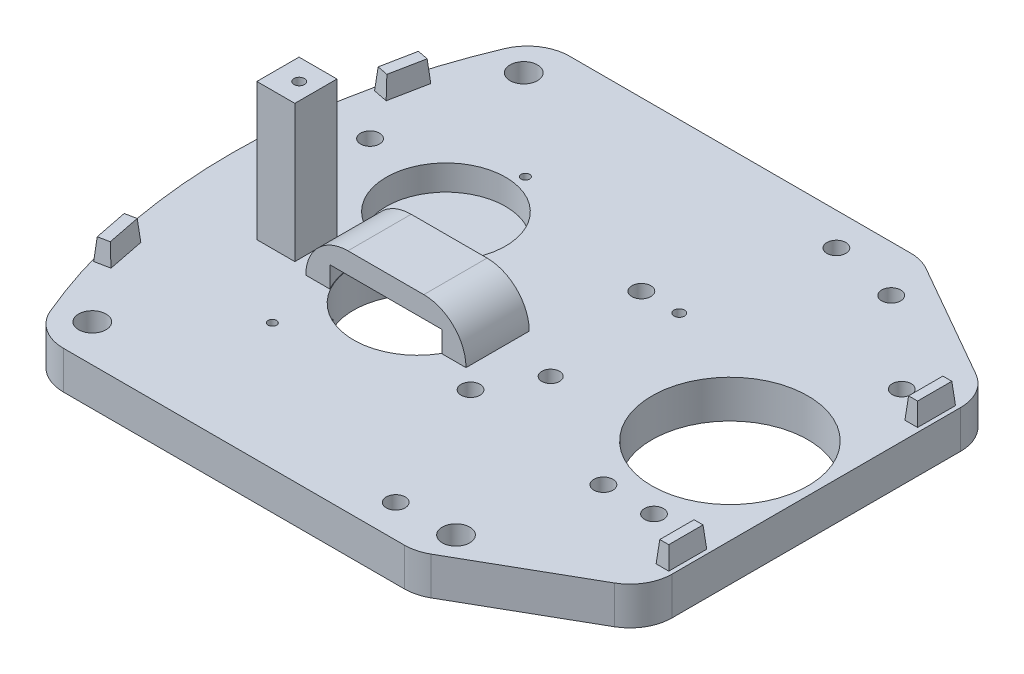
SolidWorks part; units mm, degrees
ref_plane "Front" through (0, 0, 0) normal (0, 0, 1) x (1, 0, 0)
ref_plane "Top" through (0, 0, 0) normal (0, 1, 0) x (1, 0, 0)
ref_plane "Right" through (0, 0, 0) normal (1, 0, 0) x (0, 0, -1)
sketch "Sketch1" plane through (0, 0, 0) normal (0, 1, 0) x (1, 0, 0)
  line L0 (125, 60) -> (3.8854, 60) construction
  line L1 (0, 0) -> (125, 0)
  line L2 (0, 0) -> (0, 120)
  line L3 (0, 120) -> (125, 120)
  line L4 (125, 0) -> (125, 120)
  line L5 (3.8854, 127.5) -> (3.8854, -7.5) construction
  arc A0 (3.8854, 127.5) -> (3.8854, -7.5) centre (125, 60) ccw
  dimension "D1" = 125
  dimension "D2" = 120
  dimension "D3" = 135
extrude "Top_Base" add sketch "Sketch1" along normal blind 9 contours L2 A0 | L1 L4 L3 L2 region at (62.5, 0, -60) region at (-5.4854, 0, -60)
sketch "Fingers_Position" plane through (0, 9, 0) normal (0, 1, 0) x (1, 0, 0)
  line L5 (67.75, 3.25) -> (12.75, 3.25) construction
  line L6 (67.75, 3.25) -> (67.75, 35.25) construction
  line L7 (67.75, 35.25) -> (12.75, 35.25) construction
  line L8 (12.75, 3.25) -> (12.75, 35.25) construction
  line L10 (67.75, 19.25) -> (26, 19.25) construction
  line L11 (77.75, 104.5) -> (77.75, 49.5) construction
  line L12 (35.75, 35.25) -> (35.75, 3.25) construction
  line L13 (40.75, 35.25) -> (40.75, 3.25) construction
  line L14 (125, 60) -> (-13.6542, 60) construction
  line L15 (35.75, 84.75) -> (35.75, 116.75) construction
  line L16 (26, 19.25) -> (26, 30) construction
  line L18 (77.75, 49.5) -> (109.75, 49.5) construction
  line L19 (109.75, 49.5) -> (109.75, 104.5) construction
  line L20 (109.75, 104.5) -> (77.75, 104.5) construction
  line L21 (92.5, 69) -> (92.5, 31) construction
  line L22 (92.5, 31) -> (116.5, 31) construction
  line L23 (116.5, 31) -> (116.5, 69) construction
  line L24 (116.5, 69) -> (92.5, 69) construction
  line L25 (93.75, 104.5) -> (93.75, 60) construction
  line L26 (104.5, 31) -> (104.5, 60) construction
  line L27 (26, 100.75) -> (26, 90) construction
  line L28 (40.75, 84.75) -> (40.75, 116.75) construction
  line L29 (67.75, 100.75) -> (26, 100.75) construction
  line L30 (12.75, 116.75) -> (12.75, 84.75) construction
  line L31 (67.75, 84.75) -> (12.75, 84.75) construction
  line L32 (67.75, 116.75) -> (67.75, 84.75) construction
  line L33 (67.75, 116.75) -> (12.75, 116.75) construction
  line L34 (26, 72.5) -> (26, 47.5) construction
  line L35 (92.5, 36) -> (98.5, 36) construction
  line L36 (98.5, 36) -> (98.5, 31) construction
  line L37 (116.5, 36) -> (110.5, 36) construction
  line L38 (110.5, 36) -> (110.5, 31) construction
  line L39 (93.75, 60) -> (104.5, 60) construction
  line L40 (77.75, 77.5) -> (109.75, 77.5) construction
  line L41 (125, 0) -> (125, 120) construction
  line L42 (67.75, 75.75) -> (58.75, 75.75) construction
  line L43 (67.75, 35.25) -> (58.75, 35.25) construction
  line L44 (67.75, 35.25) -> (67.75, 44.25) construction
  line L45 (67.75, 44.25) -> (58.75, 44.25) construction
  line L46 (58.75, 35.25) -> (58.75, 44.25) construction
  line L47 (58.75, 84.75) -> (58.75, 75.75) construction
  line L48 (67.75, 84.75) -> (58.75, 84.75) construction
  line L49 (67.75, 84.75) -> (67.75, 75.75) construction
  circle A1 centre (26, 30) radius 16.25 construction
  circle A3 centre (26, 30) radius 17.5 construction
  circle A5 centre (26, 30) radius 15 construction
  circle A6 centre (104.5, 60) radius 9 construction
  circle A7 centre (104.5, 60) radius 17.75 construction
  circle A8 centre (26, 30) radius 1 construction
  circle A9 centre (39.1696, 51.25) radius 7.5 construction
  circle A10 centre (39.1696, 51.25) radius 8.75 construction
  circle A11 centre (39.1696, 51.25) radius 10 construction
  circle A12 centre (39.1696, 68.75) radius 10 construction
  circle A13 centre (39.1696, 68.75) radius 8.75 construction
  circle A14 centre (39.1696, 68.75) radius 7.5 construction
  circle A15 centre (26, 90) radius 1 construction
  circle A16 centre (26, 90) radius 15 construction
  circle A17 centre (26, 90) radius 17.5 construction
  circle A18 centre (26, 90) radius 16.25 construction
  circle A19 centre (98.5, 36) radius 2.25 construction
  circle A20 centre (110.5, 36) radius 2.25 construction
  arc A21 (0, 120) -> (0, 0) centre (125, 60) ccw construction
  dimension "D3" = 32.5
  dimension "D4" = 35
  dimension "D6" = 30
  dimension "D10" = 18
  dimension "D11" = 35.5
  dimension "D19" = 2
  dimension "D20" = 20
  dimension "D21" = 17.5
  dimension "D22" = 15
  dimension "D29" = 4.5
  dimension "D5" = 32
  dimension "D7" = 55
  dimension "D8" = 24
  dimension "D9" = 38
  dimension "D14" = 10
  dimension "D2" = 27
  dimension "D15" = 55
  dimension "D16" = 32
  dimension "D17" = 41.75
  dimension "D18" = 10.75
  dimension "D23" = 25
  dimension "D13" = 29
  dimension "D25" = 6
  dimension "D26" = 6
  dimension "D27" = 5
  dimension "D28" = 5
  dimension "D12" = 44.5
  dimension "D30" = 10.75
  dimension "D31" = 27
  dimension "D24" = 8.5
  dimension "D32" = 32
  dimension "D33" = 9
  dimension "D34" = 9
sketch "Intermediate_Gear_Position" plane through (0, 9, 0) normal (0, 1, 0) x (1, 0, 0)
  line L0 (-5.25, 73.4139) -> (23.75, 73.4139) construction
  line L1 (35.75, 84.75) -> (35.75, 116.75) construction
  line L2 (32.75, 85.4139) -> (32.75, 61.4139) construction
  line L3 (-0.25, 79.4139) -> (-0.25, 85.4139) construction
  line L4 (32.75, 85.4139) -> (-5.25, 85.4139) construction
  line L6 (-5.25, 85.4139) -> (-5.25, 61.4139) construction
  line L7 (32.75, 61.4139) -> (-5.25, 61.4139) construction
  line L21 (-0.25, 67.4139) -> (-0.25, 61.4139) construction
  circle A0 centre (39.1696, 51.25) radius 14 construction
  circle A4 centre (39.1696, 51.25) radius 15 construction
  circle A6 centre (23.75, 73.4139) radius 14 construction
  circle A8 centre (39.1696, 51.25) radius 13 construction
  circle A10 centre (-0.25, 67.4139) radius 2.25 construction
  circle A11 centre (23.75, 73.4139) radius 13 construction
  circle A12 centre (-0.25, 79.4139) radius 2.25 construction
  circle A13 centre (23.75, 73.4139) radius 12 construction
  dimension "D2" = 30
  dimension "D6" = 28
  dimension "D4" = 26
  dimension "D18" = 4.5
  dimension "D22" = 4.5
  dimension "D3" = 28
  dimension "D10" = 26
  dimension "D11" = 24
  dimension "D8" = 38
  dimension "D5" = 6
  dimension "D7" = 24
  dimension "D16" = 5
  dimension "D19" = 6
  dimension "D21" = 5
  dimension "D9" = 29
  dimension "D12" = 3
sketch "Sketch5" plane through (0, 9, 0) normal (0, 1, 0) x (1, 0, 0)
  circle A1 centre (23.75, 73.4139) radius 14.15
  dimension "D1" = 28.3
extrude "Drive_Gear_Hole" cut sketch "Sketch5" against normal blind 6
sketch "Sketch8" plane through (0, 9, 0) normal (0, 1, 0) x (1, 0, 0)
  circle A1 centre (104.5, 60) radius 18.5
  dimension "D2" = 37
sketch "Sketch28" plane through (0, 9, 0) normal (0, 1, 0) x (1, 0, 0)
  circle A0 centre (39.1696, 51.25) radius 15.15
  dimension "D1" = 30.3
extrude "Two_Stage_Gear_Hole" cut sketch "Sketch28" against normal through all
extrude "XL320_Finger_Knuckle_Mount" cut sketch "Sketch8" against normal through all
sketch "XL320_Mount_Holes" plane through (0, 9, 0) normal (0, 1, 0) x (1, 0, 0)
  line L0 (116.5, 36) -> (110.5, 36) construction
  circle A13 centre (110.5, 36) radius 2.25
  circle A15 centre (98.5, 36) radius 2.25
  circle A16 centre (-0.25, 79.4139) radius 2.25
  circle A17 centre (-0.25, 67.4139) radius 2.25
  dimension "D5" = 4.5
sketch "AX12_Mount_Holes" plane through (0, 9, 0) normal (0, 1, 0) x (1, 0, 0)
  line L0 (67.75, 116.75) -> (77.5, 116.75) construction
  line L1 (67.75, 116.75) -> (12.75, 116.75) construction
  line L2 (77.5, 116.75) -> (77.5, 112.25) construction
  line L3 (67.75, 84.75) -> (67.75, 80.25) construction
  line L4 (67.75, 80.25) -> (63.25, 80.25) construction
  line L5 (93.75, 104.5) -> (93.75, 109) construction
  line L6 (109.75, 104.5) -> (114.25, 104.5) construction
  line L7 (109.75, 104.5) -> (77.75, 104.5) construction
  line L8 (114.25, 104.5) -> (114.25, 91) construction
  line L9 (77.5, 3.25) -> (67.75, 3.25) construction
  line L10 (67.75, 35.25) -> (67.75, 39.75) construction
  line L11 (67.75, 39.75) -> (63.25, 39.75) construction
  line L13 (67.75, 3.25) -> (12.75, 3.25) construction
  line L14 (77.5, 3.25) -> (77.5, 7.75) construction
  circle A4 centre (77.5, 112.25) radius 2.25
  circle A5 centre (63.25, 80.25) radius 2.25
  circle A6 centre (114.25, 91) radius 2.25
  circle A7 centre (93.75, 109) radius 2.25
  circle A8 centre (63.25, 39.75) radius 2.25
  circle A9 centre (77.5, 7.75) radius 2.25
  dimension "D3" = 4.5
  dimension "D4" = 13.5
  dimension "D2" = 4.5
  dimension "D6" = 4.5
  dimension "D1" = 9.75
  dimension "D5" = 9.75
sketch "Sketch26" plane through (0, 9, 0) normal (0, -1, 0) x (1, 0, 0)
  line L0 (26, -12.5) -> (26, -30) construction
  line L2 (-13.6542, -60) -> (125, -60) construction
  circle A0 centre (26, -30) radius 17.5 construction
  circle A1 centre (26, -30) radius 1
  circle A2 centre (26, -90) radius 1
  dimension "D2" = 2
extrude "String_Holes" cut sketch "Sketch26" along normal through all
extrude "XL320_Mount_Holes_(M4)" cut sketch "XL320_Mount_Holes" against normal through all
extrude "AX12_Mount_Holes_(M4)" cut sketch "AX12_Mount_Holes" against normal through all
sketch "Sketch27" plane through (0, 0, 0) normal (0, -1, 0) x (1, 0, 0)
  line L0 (110.5, -31.6699) -> (106.75, -33.8349)
  line L2 (106.75, -33.8349) -> (106.75, -38.1651)
  line L3 (106.75, -38.1651) -> (110.5, -40.3301)
  line L5 (110.5, -40.3301) -> (114.25, -38.1651)
  line L6 (114.25, -38.1651) -> (114.25, -33.8349)
  line L8 (114.25, -33.8349) -> (110.5, -31.6699)
  line L13 (110.5, -31.6699) -> (110.5, -40.3301) construction
  line L14 (106.75, -33.8349) -> (114.25, -38.1651) construction
  line L16 (114.25, -33.8349) -> (106.75, -38.1651) construction
  line L17 (98.5, -31.6699) -> (94.75, -33.8349)
  line L18 (94.75, -33.8349) -> (102.25, -38.1651) construction
  line L19 (94.75, -33.8349) -> (94.75, -38.1651)
  line L20 (102.25, -33.8349) -> (94.75, -38.1651) construction
  line L21 (98.5, -31.6699) -> (98.5, -40.3301) construction
  line L22 (102.25, -38.1651) -> (102.25, -33.8349)
  line L23 (94.75, -38.1651) -> (98.5, -40.3301)
  line L24 (98.5, -40.3301) -> (102.25, -38.1651)
  line L25 (102.25, -33.8349) -> (98.5, -31.6699)
  line L26 (3.5, -65.2488) -> (-0.25, -63.0837)
  line L27 (3.5, -69.5789) -> (3.5, -65.2488)
  line L28 (-4, -65.2488) -> (-4, -69.5789)
  line L29 (-0.25, -63.0837) -> (-0.25, -71.744) construction
  line L30 (-4, -65.2488) -> (3.5, -69.5789) construction
  line L31 (-0.25, -63.0837) -> (-4, -65.2488)
  line L32 (-0.25, -71.744) -> (3.5, -69.5789)
  line L33 (-4, -69.5789) -> (-0.25, -71.744)
  line L34 (3.5, -65.2488) -> (-4, -69.5789) construction
  line L35 (-4, -77.2488) -> (3.5, -81.5789) construction
  line L36 (-4, -77.2488) -> (-4, -81.5789)
  line L37 (-0.25, -83.744) -> (3.5, -81.5789)
  line L38 (-0.25, -75.0837) -> (-4, -77.2488)
  line L39 (3.5, -81.5789) -> (3.5, -77.2488)
  line L40 (-0.25, -75.0837) -> (-0.25, -83.744) construction
  line L41 (3.5, -77.2488) -> (-0.25, -75.0837)
  line L42 (3.5, -77.2488) -> (-4, -81.5789) construction
  line L43 (-4, -81.5789) -> (-0.25, -83.744)
  circle A4 centre (110.5, -36) radius 3.75 construction
  circle A5 centre (98.5, -36) radius 3.75 construction
  circle A6 centre (98.5, -36) radius 2.25 construction
  circle A7 centre (-0.25, -67.4139) radius 3.75 construction
  circle A8 centre (-0.25, -67.4139) radius 2.25 construction
  circle A9 centre (-0.25, -79.4139) radius 3.75 construction
  circle A21 centre (-0.25, -79.4139) radius 2.25 construction
  dimension "D1" = 7.5
  dimension "D3" = 7.5
  dimension "D5" = 7.5
  dimension "D7" = 7.5
  dimension "D2" = 60
  dimension "D4" = 60
  dimension "D6" = 60
  dimension "D8" = 60
extrude "Nuts_(M4)" cut sketch "Sketch27" against normal blind 5
sketch "Sketch34" plane through (0, 0, 0) normal (0, -1, 0) x (1, 0, 0)
  circle A0 centre (26, -30) radius 15
  circle A1 centre (26, -90) radius 15
  circle A2 centre (26, -90) radius 11.75 construction
  dimension "D1" = 30
  dimension "D2" = 23.5
extrude "Holes_For_M4_In_Finger_Gear" cut sketch "Sketch34" against normal blind 2
sketch "Sketch31" plane through (0, 9, 0) normal (0, 1, 0) x (1, 0, 0)
  line L1 (58.1696, 43.75) -> (20.1696, 43.75)
  line L2 (58.1696, 43.75) -> (58.1696, 58.75)
  line L3 (58.1696, 58.75) -> (20.1696, 58.75)
  line L4 (20.1696, 43.75) -> (20.1696, 58.75)
  line L5 (58.1696, 43.75) -> (20.1696, 58.75) construction
  line L6 (58.1696, 58.75) -> (20.1696, 43.75) construction
  point P0 (39.1696, 51.25)
  dimension "D1" = 38
  dimension "D2" = 15
extrude "Boss-Extrude1" add sketch "Sketch31" along normal blind 10
sketch "Sketch32" plane through (0, 9, 0) normal (0, -1, 0) x (1, 0, 0)
  circle A0 centre (39.1696, -51.25) radius 15.25
  dimension "D1" = 30.5
extrude "Cut-Extrude5" cut sketch "Sketch32" against normal blind 5
sketch "Sketch33" plane through (0, 14, 0) normal (0, -1, 0) x (1, 0, 0)
  circle A0 centre (39.1696, -51.25) radius 1
  dimension "D1" = 2
extrude "Cut-Extrude6" cut sketch "Sketch33" against normal blind 2.5
fillet "Fillet2" radius 10 2 edges at (58.1696, 19, -51.25) (20.1696, 19, -51.25)
sketch "Sketch36" plane through (0, 9, 0) normal (0, 1, 0) x (1, 0, 0)
  line L0 (90, 120) -> (125, 100)
  line L1 (0, 120) -> (125, 120) construction
  line L2 (125, 0) -> (125, 120) construction
  line L3 (125, 100) -> (125, 120)
  line L4 (125, 120) -> (90, 120)
  line L5 (-13.6542, 60) -> (125, 60) construction
  line L6 (125, 0) -> (90, 0)
  line L7 (125, 20) -> (125, 0)
  line L8 (90, 0) -> (125, 20)
  dimension "D1" = 35
  dimension "D4" = 20
extrude "Cut-Extrude8" cut sketch "Sketch36" against normal through all
fillet "Fillet4" radius 10 6 edges at (0, 4.5, 0) (90, 4.5, 0) (125, 4.5, -20) (125, 4.5, -100) (90, 4.5, -120) (0, 4.5, -120)
sketch "Sketch37" plane through (0, 9, 0) normal (0, 1, 0) x (1, 0, 0)
  line L0 (6.4592, 120) -> (6.4592, 0) construction
  line L1 (87.3444, 120) -> (87.3444, 0) construction
  line L2 (6.4592, 111.1529) -> (4.4592, 111.1529) construction
  line L3 (4.4592, 111.1529) -> (0.9304, 118.3326) construction
  line L4 (-13.6542, 60) -> (125, 60) construction
  line L5 (4.4592, 8.8471) -> (0.9304, 1.6674) construction
  line L6 (6.4592, 8.8471) -> (4.4592, 8.8471) construction
  line L7 (91.3444, 8.2056) -> (87.3444, 8.2056) construction
  line L10 (91.3444, 8.2056) -> (89.911, 0.335) construction
  arc A0 (87.3444, 0) -> (92.3057, 1.3176) centre (87.3444, 10) ccw construction
  circle A1 centre (4.4592, 111.1529) radius 3.25
  arc A2 (6.4592, 120) -> (-2.7547, 113.8864) centre (6.4592, 110) ccw construction
  circle A3 centre (4.4592, 8.8471) radius 3.25
  circle A4 centre (91.3444, 8.2056) radius 3.25
  dimension "D1" = 6.5
  dimension "D4" = 6.5
  dimension "D2" = 8
  dimension "D3" = 2
  dimension "D5" = 4
  dimension "D6" = 8
extrude "Connect_Holes_(M6)" cut sketch "Sketch37" against normal blind 10
sketch "Sketch41" plane through (0, 9, 0) normal (0, 1, 0) x (1, 0, 0)
  line L0 (125, 60) -> (-13.6542, 60) construction
  line L1 (125, 60) -> (65, 60) construction
  line L2 (125, 25.8032) -> (125, 94.1968) construction
  line L3 (65, 60) -> (65, 52) construction
  line L4 (65, 52) -> (70, 52) construction
  circle A1 centre (70, 52) radius 2.1
  dimension "D2" = 4.2
  dimension "D1" = 60
  dimension "D3" = 8
  dimension "D4" = 5
extrude "Connect_To_House_(M4)" cut sketch "Sketch41" against normal through all
sketch "Sketch42" plane through (0, 9, 0) normal (0, 1, 0) x (1, 0, 0)
  line L5 (-13.6542, 60) -> (125, 60) construction
  line L6 (124, 26) -> (121, 26)
  line L7 (124, 26) -> (124, 35)
  line L8 (124, 35) -> (121, 35)
  line L9 (121, 26) -> (121, 35)
  line L10 (-13.6542, 60) -> (-3.3496, 8.0542) construction
  line L11 (-9.5334, 30.2329) -> (-6.1003, 30.9139)
  line L12 (-6.1003, 30.9139) -> (-4.349, 22.0859)
  line L13 (-4.349, 22.0859) -> (-7.7822, 21.4049)
  line L14 (-7.7822, 21.4049) -> (-9.5334, 30.2329)
  line L15 (125, 25.8032) -> (125, 94.1968) construction
  line L16 (-4.349, 97.9141) -> (-7.7822, 98.5951)
  line L17 (-6.1003, 89.0861) -> (-4.349, 97.9141)
  line L18 (-7.7822, 98.5951) -> (-9.5334, 89.7671)
  line L19 (-9.5334, 89.7671) -> (-6.1003, 89.0861)
  line L20 (124, 94) -> (121, 94)
  line L21 (121, 94) -> (121, 85)
  line L22 (124, 85) -> (121, 85)
  line L23 (124, 94) -> (124, 85)
  arc A1 (-2.7547, 6.1136) -> (6.4592, 0) centre (6.4592, 10) ccw construction
  point P16 (-7.8168, 30.5734)
  dimension "D1" = 3
  dimension "D2" = 9
  dimension "D3" = 25
  dimension "D4" = 9
  dimension "D5" = 3.5
  dimension "D6" = 30
  dimension "D7" = 1
extrude "Housing_Fits" add sketch "Sketch42" along normal blind 5 draft 5
sketch "Sketch43" plane through (0, 0, 0) normal (0, -1, 0) x (1, 0, 0)
  circle A0 centre (39.1696, -68.75) radius 1
  dimension "D1" = 2
extrude "M2_Shaft_Hole" cut sketch "Sketch43" against normal blind 2
sketch "Sketch54" plane through (0, 2, 0) normal (0, -1, 0) x (1, 0, 0)
  circle A0 centre (26, -30) radius 1.5
  circle A1 centre (26, -90) radius 1.5
  dimension "D1" = 3
extrude "Hollow_Shaft_Hole" cut sketch "Sketch54" against normal blind 5
sketch "Sketch46" plane through (0, 9, 0) normal (0, 1, 0) x (1, 0, 0)
  line L0 (67.75, 84.75) -> (76.75, 75.75) construction
  line L1 (67.75, 84.75) -> (76.75, 84.75) construction
  line L2 (67.75, 84.75) -> (67.75, 75.75) construction
  line L3 (67.75, 75.75) -> (76.75, 75.75) construction
  line L4 (76.75, 84.75) -> (76.75, 75.75) construction
  line L5 (76.75, 84.75) -> (67.75, 75.75) construction
  circle A0 centre (72.25, 80.25) radius 1.25
  dimension "D3" = 2.5
  dimension "D1" = 9
  dimension "D2" = 9
extrude "Cut-Extrude11" cut sketch "Sketch46" against normal through all
sketch "Sketch47" plane through (0, 0, 0) normal (0, -1, 0) x (1, 0, 0)
  circle A0 centre (72.25, -80.25) radius 1.75
  dimension "D1" = 3.5
extrude "Cut-Extrude12" cut sketch "Sketch47" against normal blind 5
sketch "Sketch48" plane through (0, 0, 0) normal (0, -1, 0) x (1, 0, 0)
  circle A0 centre (72.25, -80.25) radius 2.5
  dimension "D1" = 5
extrude "Cut-Extrude13" cut sketch "Sketch48" against normal blind 0.75
sketch "Sketch49" plane through (0, 9, 0) normal (0, 1, 0) x (1, 0, 0)
  line L0 (-13.6542, 60) -> (12.1321, 60) construction
  line L1 (125, 60) -> (-13.6542, 60) construction
  line L2 (12.1321, 60) -> (12.1321, 50.2322) construction
  line L3 (12.1321, 50.2322) -> (12.1321, 45.2322) construction
  line L4 (12.1321, 45.2322) -> (7.0937, 45.2322)
  line L5 (7.0937, 45.2322) -> (7.0937, 55.2322)
  line L6 (7.0937, 55.2322) -> (12.1321, 55.2322)
  line L7 (12.1321, 55.2322) -> (16.0937, 55.2322)
  line L8 (16.0937, 55.2322) -> (16.0937, 45.2322)
  line L9 (16.0937, 45.2322) -> (12.1321, 45.2322)
  arc A0 (-2.7547, 113.8864) -> (-2.7547, 6.1136) centre (125, 60) ccw construction
  circle A1 centre (12.1321, 50.2322) radius 1.25
  dimension "D3" = 2.5
  dimension "D1" = 25.7863
  dimension "D2" = 9.7678
  dimension "D4" = 5
  dimension "D5" = 5.0384
  dimension "D6" = 10
  dimension "D7" = 3.9616
extrude "Boss-Extrude2" add sketch "Sketch49" along normal blind 32.5 contours L9 L8 L7 L6 L5 L4 A1 region at (9.6129, 9, -45.3667)
sketch "Sketch51" plane through (0, 9, 0) normal (0, 1, 0) x (1, 0, 0)
  circle A0 centre (12.1321, 50.2322) radius 1.25
  dimension "D1" = 2.5
extrude "Cut-Extrude14" cut sketch "Sketch51" against normal through all
sketch "Sketch52" plane through (0, 0, 0) normal (0, -1, 0) x (1, 0, 0)
  circle A0 centre (12.1321, -50.2322) radius 1.75
  dimension "D1" = 3.5
extrude "Cut-Extrude15" cut sketch "Sketch52" against normal blind 5
sketch "Sketch53" plane through (0, 0, 0) normal (0, -1, 0) x (1, 0, 0)
  circle A0 centre (12.1321, -50.2322) radius 2.5
  dimension "D1" = 5
extrude "Cut-Extrude16" cut sketch "Sketch53" against normal blind 0.75
fillet "Fillet5" radius 0.5 2 edges at (72.25, 0, -82.75) (12.1321, 0, -52.7322)
equation "\"od1\"= 35'outside diameter finger"
equation "\"n1\"= 26'number of teeth finger"
equation "\"m1\"= \"od1\" / ( \"n1\" + 2 )'module finger"
equation "\"p1\"= \"m1\" * pi'pitch finger"
equation "\"d1\"= \"m1\" * \"n1\"'primitive diameter finger"
equation "\"da1\"= \"d1\" + 2 * \"m1\"'head diamater finger"
equation "\"df1\"= \"d1\" - 2 * \"m1\"'foot diameter finger"
equation "\"od2\"= 20'outside diameter intermediate"
equation "\"n2\"= 14'number of teeth intermediate"
equation "\"m2\"= \"od2\" / ( \"n2\" + 2 )'module intermediate"
equation "\"p2\"= \"m2\" * pi'pitch intermediate"
equation "\"d2\"= \"m2\" * \"n2\"'primitive diameter intermediate"
equation "\"da2\"= \"d2\" + 2 * \"m2\"'head diamater intermediate"
equation "\"df2\"= \"d2\" - 2 * \"m2\"'foot diameter intermediate"
equation "\"od3\"= 30'outside diameter top"
equation "\"n3\"= 28'number of teeth top"
equation "\"m3\"= \"od3\" / ( \"n3\" + 2 )'module top"
equation "\"p3\"= \"m3\" * pi'pitch top"
equation "\"d3\"= \"m3\" * \"n3\"'primitive diameter top"
equation "\"da3\"= \"d3\" + 2 * \"m3\"'head diamater top"
equation "\"df3\"= \"d3\" - 2 * \"m3\"'foot diameter top"
equation "\"od4\"= 28'outside diameter drive"
equation "\"n4\"= 26'number of teeth drive"
equation "\"m4\"= \"od4\" / ( \"n4\" + 2 )'module drive"
equation "\"p4\"= \"m4\" * pi'pitch drive"
equation "\"d4\"= \"m4\" * \"n4\"'primitive diameter drive"
equation "\"da4\"= \"d4\" + 2 * \"m4\"'head diamater drive"
equation "\"df4\"= \"d4\" - 2 * \"m4\"'foot diameter drive"
equation "\"D4@Fingers_Position\"=\"da1\""
equation "\"D3@Fingers_Position\"=\"d1\""
equation "\"D6@Fingers_Position\"=\"df1\""
equation "\"D20@Fingers_Position\"=\"da2\""
equation "\"D21@Fingers_Position\"=\"d2\""
equation "\"D22@Fingers_Position\"=\"df2\""
equation "\"D3@Intermediate_Gear_Position\"=\"d3\""
equation "\"D2@Intermediate_Gear_Position\"=\"da3\""
equation "\"D4@Intermediate_Gear_Position\"=\"df3\""
equation "\"D6@Intermediate_Gear_Position\"=\"da4\""
equation "\"D10@Intermediate_Gear_Position\"=\"d4\""
equation "\"D11@Intermediate_Gear_Position\"=\"df4\""
equation "\"D1@Sketch34\"=\"df1\""
